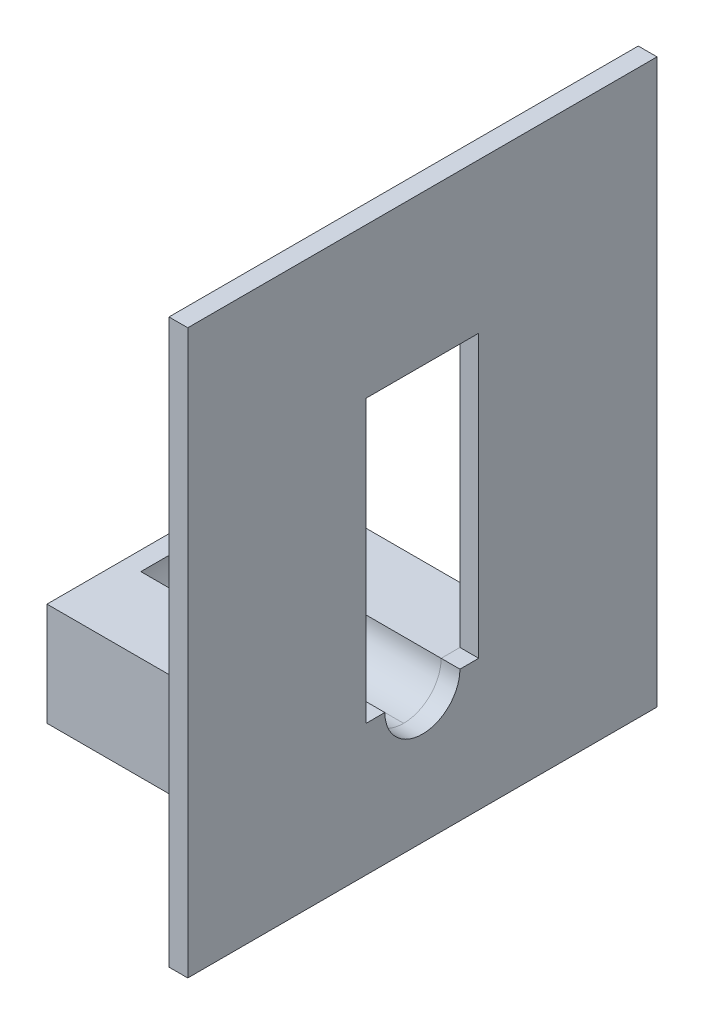
SolidWorks part; units mm, degrees
ref_plane "前视" through (0, 0, 0) normal (0, 0, 1) x (1, 0, 0)
ref_plane "上视" through (0, 0, 0) normal (0, 1, 0) x (1, 0, 0)
ref_plane "右视" through (0, 0, 0) normal (1, 0, 0) x (0, 0, -1)
sketch "Sketch1" plane through (0, 0, 0) normal (0, 1, 0) x (1, 0, 0)
  line L1 (-6.5, -6) -> (6.5, -6)
  line L2 (-6.5, -6) -> (-6.5, 6)
  line L3 (-6.5, 6) -> (6.5, 6)
  line L4 (6.5, -6) -> (6.5, 6)
  line L5 (-6.5, -6) -> (6.5, 6) construction
  line L6 (-6.5, 6) -> (6.5, -6) construction
  point P0 (0, 0)
  dimension "D1" = 12
  dimension "D2" = 13
extrude "Boss-Extrude1" add sketch "Sketch1" along normal blind 2.5
sketch "Sketch2" plane through (0, 0, 0) normal (0, -1, 0) x (1, 0, 0)
  line L0 (6.5, 6) -> (6.5, -6) construction
  line L1 (-6.5, 6) -> (6.5, 6)
  line L2 (-6.5, 6) -> (-6.5, 4)
  line L3 (-6.5, 4) -> (6.5, 4)
  line L4 (6.5, 6) -> (6.5, 4)
  line L6 (-6.5, -6) -> (6.5, -6)
  line L7 (-6.5, -6) -> (-6.5, -4)
  line L8 (-6.5, -4) -> (6.5, -4)
  line L9 (6.5, -6) -> (6.5, -4)
  dimension "D1" = 8
extrude "Boss-Extrude2" add sketch "Sketch2" along normal blind 3
sketch "Sketch3" plane through (0, 2.5, 0) normal (0, 1, 0) x (1, 0, 0)
  line L1 (6.5, -6) -> (6.5, 6) construction
  line L2 (-5.5, -2) -> (6.5, -2)
  line L3 (-5.5, -2) -> (-5.5, 2)
  line L4 (-5.5, 2) -> (6.5, 2)
  line L5 (6.5, -2) -> (6.5, 2)
  line L6 (-5.5, 0) -> (6.5, 0) construction
  line L7 (-6.5, 6) -> (-6.5, -6) construction
  dimension "D1" = 4
  dimension "D2" = 1
extrude "Cut-Extrude2" cut sketch "Sketch3" against normal blind 2
fillet "Fillet1" radius 2 3 edges at (0.5, 0.5, 2) (0.5, 0.5, -2) (-5.5, 0.5, 0)
sketch "Sketch4" plane through (6.5, 0, 0) normal (1, 0, 0) x (0, 0, -1)
  line L0 (0, 25.5) -> (0, -4.5) construction
  line L1 (-12.5, 25.5) -> (12.5, 25.5)
  line L2 (-12.5, 25.5) -> (-12.5, -4.5)
  line L3 (-12.5, -4.5) -> (12.5, -4.5)
  line L4 (12.5, 25.5) -> (12.5, -4.5)
  line L5 (2, 2.5) -> (-2, 2.5) construction
  line L7 (-3, 2.5) -> (-3, 17.5)
  line L8 (-3, 17.5) -> (3, 17.5)
  line L9 (3, 2.5) -> (3, 17.5)
  line L10 (2, 2.5) -> (6, 2.5) construction
  line L11 (-2, 2.5) -> (-3, 2.5)
  line L12 (-6, 2.5) -> (-2, 2.5) construction
  line L13 (2, 2.5) -> (3, 2.5)
  arc A0 (-2, 2.5) -> (2, 2.5) centre (0, 2.5) ccw
  dimension "D1" = 25
  dimension "D2" = 30
  dimension "D3" = 25
  dimension "D4" = 17
  dimension "D5" = 6
extrude "Boss-Extrude5" add sketch "Sketch4" along normal blind 1 separate body
